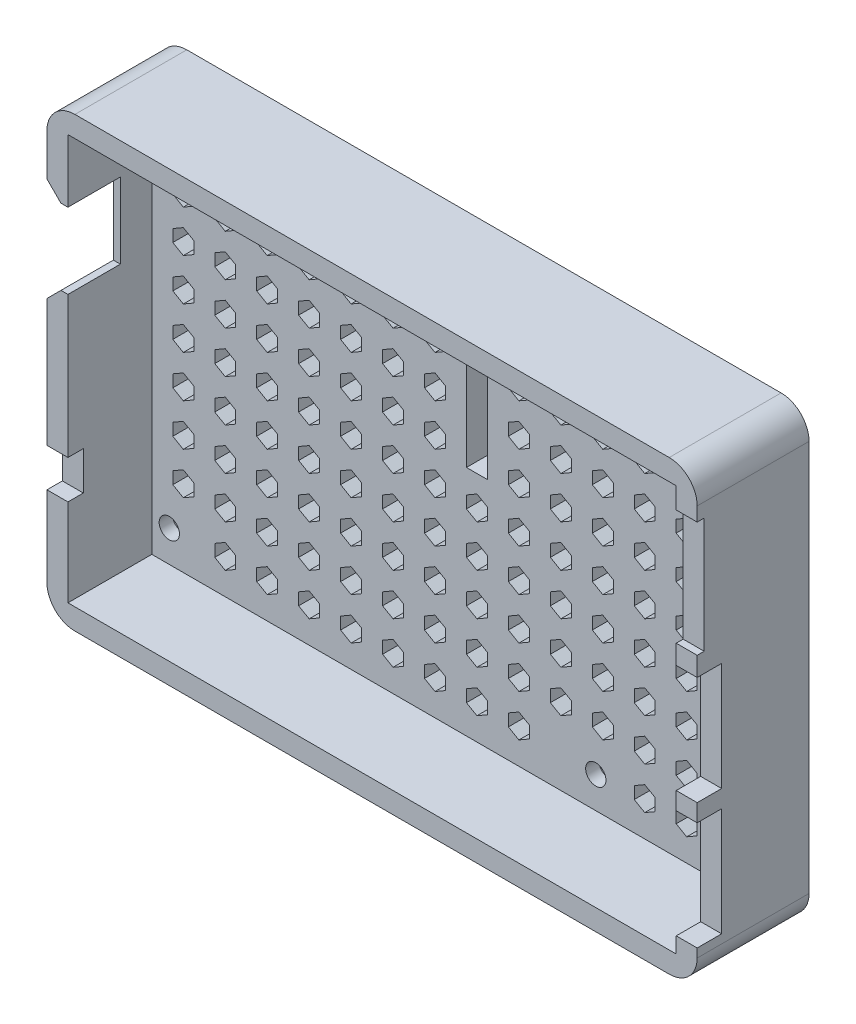
SolidWorks part; units mm, degrees
ref_plane "Přední rovina" through (0, 0, 0) normal (0, 0, 1) x (1, 0, 0)
ref_plane "Horní rovina" through (0, 0, 0) normal (0, 1, 0) x (1, 0, 0)
ref_plane "Pravá rovina" through (0, 0, 0) normal (1, 0, 0) x (0, 0, -1)
sketch "Base sketch" plane through (0, 0, 0) normal (0, 0, 1) x (1, 0, 0)
  line L1 (-46.5, 32) -> (46.5, 32)
  line L2 (-46.5, 32) -> (-46.5, -32)
  line L3 (-46.5, -32) -> (46.5, -32)
  line L4 (46.5, 32) -> (46.5, -32)
  line L5 (-46.5, 32) -> (46.5, -32) construction
  line L6 (-46.5, -32) -> (46.5, 32) construction
  point P0 (0, 0)
  dimension "D1" = 93
  dimension "D2" = 64
extrude "Base" add sketch "Base sketch" along normal blind 16
sketch "Inside cut sketch" plane through (0, 0, 16) normal (0, 0, 1) x (1, 0, 0)
  line L1 (-43.5, 29) -> (43.5, 29)
  line L2 (-43.5, 29) -> (-43.5, -29)
  line L3 (-43.5, -29) -> (43.5, -29)
  line L4 (43.5, 29) -> (43.5, -29)
  line L5 (-43.5, 29) -> (43.5, -29) construction
  line L6 (-43.5, -29) -> (43.5, 29) construction
  point P0 (0, 0)
  dimension "D1" = 58
  dimension "D2" = 87
extrude "Inside cut" cut sketch "Inside cut sketch" against normal blind 12
sketch "Front connectors sketch" plane through (46.5, 0, 0) normal (1, 0, 0) x (0, 0, -1)
  line L0 (-15, -32) -> (-15, 32)
  line L1 (-16, -32) -> (0, -32) construction
  line L2 (-16, 32) -> (0, 32) construction
  line L3 (-12.5, -32) -> (-12.5, 32)
  line L4 (-16, -32) -> (-16, 32) construction
  line L5 (-15, 26) -> (-16, 26)
  line L6 (-15, 26) -> (-15, 9.5)
  line L7 (-15, 9.5) -> (-16, 9.5)
  line L8 (-16, 26) -> (-16, 9.5)
  line L10 (-12.5, 6.75) -> (-16, 6.75)
  line L11 (-12.5, 6.75) -> (-12.5, -8.75)
  line L12 (-12.5, -8.75) -> (-16, -8.75)
  line L13 (-16, 6.75) -> (-16, -8.75)
  line L14 (-12.5, -11.25) -> (-16, -11.25)
  line L15 (-12.5, -11.25) -> (-12.5, -26.75)
  line L16 (-12.5, -26.75) -> (-16, -26.75)
  line L17 (-16, -11.25) -> (-16, -26.75)
  point P23 (-16, 17.75)
  point P25 (-16, -1)
  point P26 (-16, -19)
  dimension "D1" = 1
  dimension "D2" = 3.5
  dimension "D3" = 16.5
  dimension "D4" = 11.25
  dimension "D5" = 30
  dimension "D6" = 15.5
  dimension "D7" = 48
extrude "Front connectors" cut sketch "Front connectors sketch" against normal up to next contours L14 L17 L16 L15 | L12 L13 L10 L11 | L8 L7 L6 L5
sketch "Back connectors sketch" plane through (-46.5, 0, 0) normal (-1, 0, 0) x (0, 0, 1)
  line L0 (16, 32) -> (16, -32) construction
  line L1 (16, 20) -> (8.5, 20)
  line L2 (16, 20) -> (16, 9.2)
  line L3 (16, 9.2) -> (8.5, 9.2)
  line L4 (8.5, 20) -> (8.5, 9.2)
  line L6 (16, -11) -> (13.8, -11)
  line L7 (16, -11) -> (16, -16.5)
  line L8 (16, -16.5) -> (13.8, -16.5)
  line L9 (13.8, -11) -> (13.8, -16.5)
  dimension "D1" = 15.5
  dimension "D2" = 5.5
  dimension "D3" = 2.2
  dimension "D4" = 12
  dimension "D5" = 10.8
  dimension "D6" = 7.5
extrude "Back connectors" cut sketch "Back connectors sketch" against normal up to next
chamfer "Molex angle" distance 2 angle 45 3 edges at (-46.5, 9.2, 12.25) (-46.5, 20, 12.25) (-46.5, 14.6, 8.5)
sketch "Screw holes sketch" plane through (0, 0, 0) normal (0, 0, -1) x (-1, 0, 0)
  line L1 (-20, 24.5) -> (41, 24.5)
  line L2 (-20, 24.5) -> (-20, -24.5)
  line L3 (-20, -24.5) -> (41, -24.5)
  line L4 (41, 24.5) -> (41, -24.5)
  line L5 (-20, 24.5) -> (41, -24.5) construction
  line L6 (-20, -24.5) -> (41, 24.5) construction
  point P0 (10.5, 0)
  dimension "D1" = 5.5
  dimension "D2" = 7.5
  dimension "D3" = 49
  dimension "D4" = 61
hole_wizard "Screw holes" positions "Skica6" profile "Skica7" counterbore size "M2.5" standard "ISO" end condition through all
sketch "Skica6" plane through (0, 0, 0) normal (0, 0, -1) x (-1, 0, 0)
  point P0 (-20, -24.5)
  point P3 (-20, 24.5)
  point P6 (41, 24.5)
  point P9 (41, -24.5)
sketch "Skica7" plane through (20, -24.5, 0) normal (1, 0, 0) x (0, 1, 0)
  line L0 (0, 0) -> (0, 16)
  line L1 (0, 16) -> (1.45, 16)
  line L3 (1.45, 16) -> (1.45, 2.1)
  line L4 (1.45, 2.1) -> (3, 2.1)
  line L5 (3, 2.1) -> (3, 0)
  line L7 (3, 0) -> (0, 0)
  line L11 (0, -6.35) -> (0, 107.95) construction
  dimension "Průměr díry skrz" = 2.9
  dimension "Hloubka díry skrz" = 16
  dimension "Průměr válcového zahloubení" = 6
  dimension "Hloubka válcového zahloubení" = 2.1
fillet "Box rounding" radius 4 4 edges at (-46.5, -32, 8) (-46.5, 32, 8) (46.5, 32, 8) (46.5, -32, 8)
sketch "Ventilation holes sketch" plane through (0, 0, 0) normal (0, 0, -1) x (-1, 0, 0)
  line L0 (-42.5, 32) -> (42.5, 32) construction
  line L1 (-39, 22.2659) -> (-37.5, 23.1319)
  line L2 (-37.5, 23.1319) -> (-37.5, 24.864)
  line L3 (-37.5, 24.864) -> (-39, 25.73)
  line L4 (-39, 25.73) -> (-40.5, 24.864)
  line L5 (-40.5, 24.864) -> (-40.5, 23.1319)
  line L6 (-40.5, 23.1319) -> (-39, 22.2659)
  line L7 (-46.5, -28) -> (-46.5, 28) construction
  line L8 (-33, 22.2659) -> (-31.5, 23.1319)
  line L9 (-31.5, 23.1319) -> (-31.5, 24.864)
  line L10 (-31.5, 24.864) -> (-33, 25.73)
  line L11 (-33, 25.73) -> (-34.5, 24.864)
  line L12 (-34.5, 24.864) -> (-34.5, 23.1319)
  line L13 (-34.5, 23.1319) -> (-33, 22.2659)
  line L14 (-27, 22.2659) -> (-25.5, 23.1319)
  line L15 (-25.5, 23.1319) -> (-25.5, 24.864)
  line L16 (-25.5, 24.864) -> (-27, 25.73)
  line L17 (-27, 25.73) -> (-28.5, 24.864)
  line L18 (-28.5, 24.864) -> (-28.5, 23.1319)
  line L19 (-28.5, 23.1319) -> (-27, 22.2659)
  line L20 (-21, 22.2659) -> (-19.5, 23.1319)
  line L21 (-19.5, 23.1319) -> (-19.5, 24.864)
  line L22 (-19.5, 24.864) -> (-21, 25.73)
  line L23 (-21, 25.73) -> (-22.5, 24.864)
  line L24 (-22.5, 24.864) -> (-22.5, 23.1319)
  line L25 (-22.5, 23.1319) -> (-21, 22.2659)
  line L26 (-15, 22.2659) -> (-13.5, 23.1319)
  line L27 (-13.5, 23.1319) -> (-13.5, 24.864)
  line L28 (-13.5, 24.864) -> (-15, 25.73)
  line L29 (-15, 25.73) -> (-16.5, 24.864)
  line L30 (-16.5, 24.864) -> (-16.5, 23.1319)
  line L31 (-16.5, 23.1319) -> (-15, 22.2659)
  line L32 (-9, 22.2659) -> (-7.5, 23.1319)
  line L33 (-7.5, 23.1319) -> (-7.5, 24.864)
  line L34 (-7.5, 24.864) -> (-9, 25.73)
  line L35 (-9, 25.73) -> (-10.5, 24.864)
  line L36 (-10.5, 24.864) -> (-10.5, 23.1319)
  line L37 (-10.5, 23.1319) -> (-9, 22.2659)
  line L38 (-3, 22.2659) -> (-1.5, 23.1319)
  line L39 (-1.5, 23.1319) -> (-1.5, 24.864)
  line L40 (-1.5, 24.864) -> (-3, 25.73)
  line L41 (-3, 25.73) -> (-4.5, 24.864)
  line L42 (-4.5, 24.864) -> (-4.5, 23.1319)
  line L43 (-4.5, 23.1319) -> (-3, 22.2659)
  line L44 (3, 22.2659) -> (4.5, 23.1319)
  line L45 (4.5, 23.1319) -> (4.5, 24.864)
  line L46 (4.5, 24.864) -> (3, 25.73)
  line L47 (3, 25.73) -> (1.5, 24.864)
  line L48 (1.5, 24.864) -> (1.5, 23.1319)
  line L49 (1.5, 23.1319) -> (3, 22.2659)
  line L50 (9, 22.2659) -> (10.5, 23.1319)
  line L51 (10.5, 23.1319) -> (10.5, 24.864)
  line L52 (10.5, 24.864) -> (9, 25.73)
  line L53 (9, 25.73) -> (7.5, 24.864)
  line L54 (7.5, 24.864) -> (7.5, 23.1319)
  line L55 (7.5, 23.1319) -> (9, 22.2659)
  line L56 (15, 22.2659) -> (16.5, 23.1319)
  line L57 (16.5, 23.1319) -> (16.5, 24.864)
  line L58 (16.5, 24.864) -> (15, 25.73)
  line L59 (15, 25.73) -> (13.5, 24.864)
  line L60 (13.5, 24.864) -> (13.5, 23.1319)
  line L61 (13.5, 23.1319) -> (15, 22.2659)
  line L62 (21, 22.2659) -> (22.5, 23.1319)
  line L63 (22.5, 23.1319) -> (22.5, 24.864)
  line L64 (22.5, 24.864) -> (21, 25.73)
  line L65 (21, 25.73) -> (19.5, 24.864)
  line L66 (19.5, 24.864) -> (19.5, 23.1319)
  line L67 (19.5, 23.1319) -> (21, 22.2659)
  line L68 (27, 22.2659) -> (28.5, 23.1319)
  line L69 (28.5, 23.1319) -> (28.5, 24.864)
  line L70 (28.5, 24.864) -> (27, 25.73)
  line L71 (27, 25.73) -> (25.5, 24.864)
  line L72 (25.5, 24.864) -> (25.5, 23.1319)
  line L73 (25.5, 23.1319) -> (27, 22.2659)
  line L74 (33, 22.2659) -> (34.5, 23.1319)
  line L75 (34.5, 23.1319) -> (34.5, 24.864)
  line L76 (34.5, 24.864) -> (33, 25.73)
  line L77 (33, 25.73) -> (31.5, 24.864)
  line L78 (31.5, 24.864) -> (31.5, 23.1319)
  line L79 (31.5, 23.1319) -> (33, 22.2659)
  line L80 (39, 22.2659) -> (40.5, 23.1319)
  line L81 (40.5, 23.1319) -> (40.5, 24.864)
  line L82 (40.5, 24.864) -> (39, 25.73)
  line L83 (39, 25.73) -> (37.5, 24.864)
  line L84 (37.5, 24.864) -> (37.5, 23.1319)
  line L85 (37.5, 23.1319) -> (39, 22.2659)
  line L86 (-33, 16.2659) -> (-31.5, 17.1319)
  line L87 (-31.5, 17.1319) -> (-31.5, 18.864)
  line L88 (-31.5, 18.864) -> (-33, 19.73)
  line L89 (-33, 19.73) -> (-34.5, 18.864)
  line L90 (-34.5, 18.864) -> (-34.5, 17.1319)
  line L91 (-34.5, 17.1319) -> (-33, 16.2659)
  line L92 (-27, 16.2659) -> (-25.5, 17.1319)
  line L93 (-25.5, 17.1319) -> (-25.5, 18.864)
  line L94 (-25.5, 18.864) -> (-27, 19.73)
  line L95 (-27, 19.73) -> (-28.5, 18.864)
  line L96 (-28.5, 18.864) -> (-28.5, 17.1319)
  line L97 (-28.5, 17.1319) -> (-27, 16.2659)
  line L98 (-21, 16.2659) -> (-19.5, 17.1319)
  line L99 (-19.5, 17.1319) -> (-19.5, 18.864)
  line L100 (-19.5, 18.864) -> (-21, 19.73)
  line L101 (-21, 19.73) -> (-22.5, 18.864)
  line L102 (-22.5, 18.864) -> (-22.5, 17.1319)
  line L103 (-22.5, 17.1319) -> (-21, 16.2659)
  line L104 (-15, 16.2659) -> (-13.5, 17.1319)
  line L105 (-13.5, 17.1319) -> (-13.5, 18.864)
  line L106 (-13.5, 18.864) -> (-15, 19.73)
  line L107 (-15, 19.73) -> (-16.5, 18.864)
  line L108 (-16.5, 18.864) -> (-16.5, 17.1319)
  line L109 (-16.5, 17.1319) -> (-15, 16.2659)
  line L110 (-9, 16.2659) -> (-7.5, 17.1319)
  line L111 (-7.5, 17.1319) -> (-7.5, 18.864)
  line L112 (-7.5, 18.864) -> (-9, 19.73)
  line L113 (-9, 19.73) -> (-10.5, 18.864)
  line L114 (-10.5, 18.864) -> (-10.5, 17.1319)
  line L115 (-10.5, 17.1319) -> (-9, 16.2659)
  line L116 (-3, 16.2659) -> (-1.5, 17.1319)
  line L117 (-1.5, 17.1319) -> (-1.5, 18.864)
  line L118 (-1.5, 18.864) -> (-3, 19.73)
  line L119 (-3, 19.73) -> (-4.5, 18.864)
  line L120 (-4.5, 18.864) -> (-4.5, 17.1319)
  line L121 (-4.5, 17.1319) -> (-3, 16.2659)
  line L122 (3, 16.2659) -> (4.5, 17.1319)
  line L123 (4.5, 17.1319) -> (4.5, 18.864)
  line L124 (4.5, 18.864) -> (3, 19.73)
  line L125 (3, 19.73) -> (1.5, 18.864)
  line L126 (1.5, 18.864) -> (1.5, 17.1319)
  line L127 (1.5, 17.1319) -> (3, 16.2659)
  line L128 (9, 16.2659) -> (10.5, 17.1319)
  line L129 (10.5, 17.1319) -> (10.5, 18.864)
  line L130 (10.5, 18.864) -> (9, 19.73)
  line L131 (9, 19.73) -> (7.5, 18.864)
  line L132 (7.5, 18.864) -> (7.5, 17.1319)
  line L133 (7.5, 17.1319) -> (9, 16.2659)
  line L134 (15, 16.2659) -> (16.5, 17.1319)
  line L135 (16.5, 17.1319) -> (16.5, 18.864)
  line L136 (16.5, 18.864) -> (15, 19.73)
  line L137 (15, 19.73) -> (13.5, 18.864)
  line L138 (13.5, 18.864) -> (13.5, 17.1319)
  line L139 (13.5, 17.1319) -> (15, 16.2659)
  line L140 (21, 16.2659) -> (22.5, 17.1319)
  line L141 (22.5, 17.1319) -> (22.5, 18.864)
  line L142 (22.5, 18.864) -> (21, 19.73)
  line L143 (21, 19.73) -> (19.5, 18.864)
  line L144 (19.5, 18.864) -> (19.5, 17.1319)
  line L145 (19.5, 17.1319) -> (21, 16.2659)
  line L146 (27, 16.2659) -> (28.5, 17.1319)
  line L147 (28.5, 17.1319) -> (28.5, 18.864)
  line L148 (28.5, 18.864) -> (27, 19.73)
  line L149 (27, 19.73) -> (25.5, 18.864)
  line L150 (25.5, 18.864) -> (25.5, 17.1319)
  line L151 (25.5, 17.1319) -> (27, 16.2659)
  line L152 (33, 16.2659) -> (34.5, 17.1319)
  line L153 (34.5, 17.1319) -> (34.5, 18.864)
  line L154 (34.5, 18.864) -> (33, 19.73)
  line L155 (33, 19.73) -> (31.5, 18.864)
  line L156 (31.5, 18.864) -> (31.5, 17.1319)
  line L157 (31.5, 17.1319) -> (33, 16.2659)
  line L158 (39, 16.2659) -> (40.5, 17.1319)
  line L159 (40.5, 17.1319) -> (40.5, 18.864)
  line L160 (40.5, 18.864) -> (39, 19.73)
  line L161 (39, 19.73) -> (37.5, 18.864)
  line L162 (37.5, 18.864) -> (37.5, 17.1319)
  line L163 (37.5, 17.1319) -> (39, 16.2659)
  line L164 (-33, 10.2659) -> (-31.5, 11.1319)
  line L165 (-31.5, 11.1319) -> (-31.5, 12.864)
  line L166 (-31.5, 12.864) -> (-33, 13.73)
  line L167 (-33, 13.73) -> (-34.5, 12.864)
  line L168 (-34.5, 12.864) -> (-34.5, 11.1319)
  line L169 (-34.5, 11.1319) -> (-33, 10.2659)
  line L170 (-27, 10.2659) -> (-25.5, 11.1319)
  line L171 (-25.5, 11.1319) -> (-25.5, 12.864)
  line L172 (-25.5, 12.864) -> (-27, 13.73)
  line L173 (-27, 13.73) -> (-28.5, 12.864)
  line L174 (-28.5, 12.864) -> (-28.5, 11.1319)
  line L175 (-28.5, 11.1319) -> (-27, 10.2659)
  line L176 (-21, 10.2659) -> (-19.5, 11.1319)
  line L177 (-19.5, 11.1319) -> (-19.5, 12.864)
  line L178 (-19.5, 12.864) -> (-21, 13.73)
  line L179 (-21, 13.73) -> (-22.5, 12.864)
  line L180 (-22.5, 12.864) -> (-22.5, 11.1319)
  line L181 (-22.5, 11.1319) -> (-21, 10.2659)
  line L182 (-15, 10.2659) -> (-13.5, 11.1319)
  line L183 (-13.5, 11.1319) -> (-13.5, 12.864)
  line L184 (-13.5, 12.864) -> (-15, 13.73)
  line L185 (-15, 13.73) -> (-16.5, 12.864)
  line L186 (-16.5, 12.864) -> (-16.5, 11.1319)
  line L187 (-16.5, 11.1319) -> (-15, 10.2659)
  line L188 (-9, 10.2659) -> (-7.5, 11.1319)
  line L189 (-7.5, 11.1319) -> (-7.5, 12.864)
  line L190 (-7.5, 12.864) -> (-9, 13.73)
  line L191 (-9, 13.73) -> (-10.5, 12.864)
  line L192 (-10.5, 12.864) -> (-10.5, 11.1319)
  line L193 (-10.5, 11.1319) -> (-9, 10.2659)
  line L194 (-3, 10.2659) -> (-1.5, 11.1319)
  line L195 (-1.5, 11.1319) -> (-1.5, 12.864)
  line L196 (-1.5, 12.864) -> (-3, 13.73)
  line L197 (-3, 13.73) -> (-4.5, 12.864)
  line L198 (-4.5, 12.864) -> (-4.5, 11.1319)
  line L199 (-4.5, 11.1319) -> (-3, 10.2659)
  line L200 (3, 10.2659) -> (4.5, 11.1319)
  line L201 (4.5, 11.1319) -> (4.5, 12.864)
  line L202 (4.5, 12.864) -> (3, 13.73)
  line L203 (3, 13.73) -> (1.5, 12.864)
  line L204 (1.5, 12.864) -> (1.5, 11.1319)
  line L205 (1.5, 11.1319) -> (3, 10.2659)
  line L206 (9, 10.2659) -> (10.5, 11.1319)
  line L207 (10.5, 11.1319) -> (10.5, 12.864)
  line L208 (10.5, 12.864) -> (9, 13.73)
  line L209 (9, 13.73) -> (7.5, 12.864)
  line L210 (7.5, 12.864) -> (7.5, 11.1319)
  line L211 (7.5, 11.1319) -> (9, 10.2659)
  line L212 (15, 10.2659) -> (16.5, 11.1319)
  line L213 (16.5, 11.1319) -> (16.5, 12.864)
  line L214 (16.5, 12.864) -> (15, 13.73)
  line L215 (15, 13.73) -> (13.5, 12.864)
  line L216 (13.5, 12.864) -> (13.5, 11.1319)
  line L217 (13.5, 11.1319) -> (15, 10.2659)
  line L218 (21, 10.2659) -> (22.5, 11.1319)
  line L219 (22.5, 11.1319) -> (22.5, 12.864)
  line L220 (22.5, 12.864) -> (21, 13.73)
  line L221 (21, 13.73) -> (19.5, 12.864)
  line L222 (19.5, 12.864) -> (19.5, 11.1319)
  line L223 (19.5, 11.1319) -> (21, 10.2659)
  line L224 (27, 10.2659) -> (28.5, 11.1319)
  line L225 (28.5, 11.1319) -> (28.5, 12.864)
  line L226 (28.5, 12.864) -> (27, 13.73)
  line L227 (27, 13.73) -> (25.5, 12.864)
  line L228 (25.5, 12.864) -> (25.5, 11.1319)
  line L229 (25.5, 11.1319) -> (27, 10.2659)
  line L230 (33, 10.2659) -> (34.5, 11.1319)
  line L231 (34.5, 11.1319) -> (34.5, 12.864)
  line L232 (34.5, 12.864) -> (33, 13.73)
  line L233 (33, 13.73) -> (31.5, 12.864)
  line L234 (31.5, 12.864) -> (31.5, 11.1319)
  line L235 (31.5, 11.1319) -> (33, 10.2659)
  line L236 (39, 10.2659) -> (40.5, 11.1319)
  line L237 (40.5, 11.1319) -> (40.5, 12.864)
  line L238 (40.5, 12.864) -> (39, 13.73)
  line L239 (39, 13.73) -> (37.5, 12.864)
  line L240 (37.5, 12.864) -> (37.5, 11.1319)
  line L241 (37.5, 11.1319) -> (39, 10.2659)
  line L242 (-33, 4.2659) -> (-31.5, 5.1319)
  line L243 (-31.5, 5.1319) -> (-31.5, 6.864)
  line L244 (-31.5, 6.864) -> (-33, 7.73)
  line L245 (-33, 7.73) -> (-34.5, 6.864)
  line L246 (-34.5, 6.864) -> (-34.5, 5.1319)
  line L247 (-34.5, 5.1319) -> (-33, 4.2659)
  line L248 (-27, 4.2659) -> (-25.5, 5.1319)
  line L249 (-25.5, 5.1319) -> (-25.5, 6.864)
  line L250 (-25.5, 6.864) -> (-27, 7.73)
  line L251 (-27, 7.73) -> (-28.5, 6.864)
  line L252 (-28.5, 6.864) -> (-28.5, 5.1319)
  line L253 (-28.5, 5.1319) -> (-27, 4.2659)
  line L254 (-21, 4.2659) -> (-19.5, 5.1319)
  line L255 (-19.5, 5.1319) -> (-19.5, 6.864)
  line L256 (-19.5, 6.864) -> (-21, 7.73)
  line L257 (-21, 7.73) -> (-22.5, 6.864)
  line L258 (-22.5, 6.864) -> (-22.5, 5.1319)
  line L259 (-22.5, 5.1319) -> (-21, 4.2659)
  line L260 (-15, 4.2659) -> (-13.5, 5.1319)
  line L261 (-13.5, 5.1319) -> (-13.5, 6.864)
  line L262 (-13.5, 6.864) -> (-15, 7.73)
  line L263 (-15, 7.73) -> (-16.5, 6.864)
  line L264 (-16.5, 6.864) -> (-16.5, 5.1319)
  line L265 (-16.5, 5.1319) -> (-15, 4.2659)
  line L266 (-9, 4.2659) -> (-7.5, 5.1319)
  line L267 (-7.5, 5.1319) -> (-7.5, 6.864)
  line L268 (-7.5, 6.864) -> (-9, 7.73)
  line L269 (-9, 7.73) -> (-10.5, 6.864)
  line L270 (-10.5, 6.864) -> (-10.5, 5.1319)
  line L271 (-10.5, 5.1319) -> (-9, 4.2659)
  line L272 (-3, 4.2659) -> (-1.5, 5.1319)
  line L273 (-1.5, 5.1319) -> (-1.5, 6.864)
  line L274 (-1.5, 6.864) -> (-3, 7.73)
  line L275 (-3, 7.73) -> (-4.5, 6.864)
  line L276 (-4.5, 6.864) -> (-4.5, 5.1319)
  line L277 (-4.5, 5.1319) -> (-3, 4.2659)
  line L278 (3, 4.2659) -> (4.5, 5.1319)
  line L279 (4.5, 5.1319) -> (4.5, 6.864)
  line L280 (4.5, 6.864) -> (3, 7.73)
  line L281 (3, 7.73) -> (1.5, 6.864)
  line L282 (1.5, 6.864) -> (1.5, 5.1319)
  line L283 (1.5, 5.1319) -> (3, 4.2659)
  line L284 (9, 4.2659) -> (10.5, 5.1319)
  line L285 (10.5, 5.1319) -> (10.5, 6.864)
  line L286 (10.5, 6.864) -> (9, 7.73)
  line L287 (9, 7.73) -> (7.5, 6.864)
  line L288 (7.5, 6.864) -> (7.5, 5.1319)
  line L289 (7.5, 5.1319) -> (9, 4.2659)
  line L290 (15, 4.2659) -> (16.5, 5.1319)
  line L291 (16.5, 5.1319) -> (16.5, 6.864)
  line L292 (16.5, 6.864) -> (15, 7.73)
  line L293 (15, 7.73) -> (13.5, 6.864)
  line L294 (13.5, 6.864) -> (13.5, 5.1319)
  line L295 (13.5, 5.1319) -> (15, 4.2659)
  line L296 (21, 4.2659) -> (22.5, 5.1319)
  line L297 (22.5, 5.1319) -> (22.5, 6.864)
  line L298 (22.5, 6.864) -> (21, 7.73)
  line L299 (21, 7.73) -> (19.5, 6.864)
  line L300 (19.5, 6.864) -> (19.5, 5.1319)
  line L301 (19.5, 5.1319) -> (21, 4.2659)
  line L302 (27, 4.2659) -> (28.5, 5.1319)
  line L303 (28.5, 5.1319) -> (28.5, 6.864)
  line L304 (28.5, 6.864) -> (27, 7.73)
  line L305 (27, 7.73) -> (25.5, 6.864)
  line L306 (25.5, 6.864) -> (25.5, 5.1319)
  line L307 (25.5, 5.1319) -> (27, 4.2659)
  line L308 (33, 4.2659) -> (34.5, 5.1319)
  line L309 (34.5, 5.1319) -> (34.5, 6.864)
  line L310 (34.5, 6.864) -> (33, 7.73)
  line L311 (33, 7.73) -> (31.5, 6.864)
  line L312 (31.5, 6.864) -> (31.5, 5.1319)
  line L313 (31.5, 5.1319) -> (33, 4.2659)
  line L314 (39, 4.2659) -> (40.5, 5.1319)
  line L315 (40.5, 5.1319) -> (40.5, 6.864)
  line L316 (40.5, 6.864) -> (39, 7.73)
  line L317 (39, 7.73) -> (37.5, 6.864)
  line L318 (37.5, 6.864) -> (37.5, 5.1319)
  line L319 (37.5, 5.1319) -> (39, 4.2659)
  line L320 (-33, -1.7341) -> (-31.5, -0.8681)
  line L321 (-31.5, -0.8681) -> (-31.5, 0.864)
  line L322 (-31.5, 0.864) -> (-33, 1.73)
  line L323 (-33, 1.73) -> (-34.5, 0.864)
  line L324 (-34.5, 0.864) -> (-34.5, -0.8681)
  line L325 (-34.5, -0.8681) -> (-33, -1.7341)
  line L326 (-27, -1.7341) -> (-25.5, -0.8681)
  line L327 (-25.5, -0.8681) -> (-25.5, 0.864)
  line L328 (-25.5, 0.864) -> (-27, 1.73)
  line L329 (-27, 1.73) -> (-28.5, 0.864)
  line L330 (-28.5, 0.864) -> (-28.5, -0.8681)
  line L331 (-28.5, -0.8681) -> (-27, -1.7341)
  line L332 (-21, -1.7341) -> (-19.5, -0.8681)
  line L333 (-19.5, -0.8681) -> (-19.5, 0.864)
  line L334 (-19.5, 0.864) -> (-21, 1.73)
  line L335 (-21, 1.73) -> (-22.5, 0.864)
  line L336 (-22.5, 0.864) -> (-22.5, -0.8681)
  line L337 (-22.5, -0.8681) -> (-21, -1.7341)
  line L338 (-15, -1.7341) -> (-13.5, -0.8681)
  line L339 (-13.5, -0.8681) -> (-13.5, 0.864)
  line L340 (-13.5, 0.864) -> (-15, 1.73)
  line L341 (-15, 1.73) -> (-16.5, 0.864)
  line L342 (-16.5, 0.864) -> (-16.5, -0.8681)
  line L343 (-16.5, -0.8681) -> (-15, -1.7341)
  line L344 (-9, -1.7341) -> (-7.5, -0.8681)
  line L345 (-7.5, -0.8681) -> (-7.5, 0.864)
  line L346 (-7.5, 0.864) -> (-9, 1.73)
  line L347 (-9, 1.73) -> (-10.5, 0.864)
  line L348 (-10.5, 0.864) -> (-10.5, -0.8681)
  line L349 (-10.5, -0.8681) -> (-9, -1.7341)
  line L350 (-3, -1.7341) -> (-1.5, -0.8681)
  line L351 (-1.5, -0.8681) -> (-1.5, 0.864)
  line L352 (-1.5, 0.864) -> (-3, 1.73)
  line L353 (-3, 1.73) -> (-4.5, 0.864)
  line L354 (-4.5, 0.864) -> (-4.5, -0.8681)
  line L355 (-4.5, -0.8681) -> (-3, -1.7341)
  line L356 (3, -1.7341) -> (4.5, -0.8681)
  line L357 (4.5, -0.8681) -> (4.5, 0.864)
  line L358 (4.5, 0.864) -> (3, 1.73)
  line L359 (3, 1.73) -> (1.5, 0.864)
  line L360 (1.5, 0.864) -> (1.5, -0.8681)
  line L361 (1.5, -0.8681) -> (3, -1.7341)
  line L362 (9, -1.7341) -> (10.5, -0.8681)
  line L363 (10.5, -0.8681) -> (10.5, 0.864)
  line L364 (10.5, 0.864) -> (9, 1.73)
  line L365 (9, 1.73) -> (7.5, 0.864)
  line L366 (7.5, 0.864) -> (7.5, -0.8681)
  line L367 (7.5, -0.8681) -> (9, -1.7341)
  line L368 (15, -1.7341) -> (16.5, -0.8681)
  line L369 (16.5, -0.8681) -> (16.5, 0.864)
  line L370 (16.5, 0.864) -> (15, 1.73)
  line L371 (15, 1.73) -> (13.5, 0.864)
  line L372 (13.5, 0.864) -> (13.5, -0.8681)
  line L373 (13.5, -0.8681) -> (15, -1.7341)
  line L374 (21, -1.7341) -> (22.5, -0.8681)
  line L375 (22.5, -0.8681) -> (22.5, 0.864)
  line L376 (22.5, 0.864) -> (21, 1.73)
  line L377 (21, 1.73) -> (19.5, 0.864)
  line L378 (19.5, 0.864) -> (19.5, -0.8681)
  line L379 (19.5, -0.8681) -> (21, -1.7341)
  line L380 (27, -1.7341) -> (28.5, -0.8681)
  line L381 (28.5, -0.8681) -> (28.5, 0.864)
  line L382 (28.5, 0.864) -> (27, 1.73)
  line L383 (27, 1.73) -> (25.5, 0.864)
  line L384 (25.5, 0.864) -> (25.5, -0.8681)
  line L385 (25.5, -0.8681) -> (27, -1.7341)
  line L386 (33, -1.7341) -> (34.5, -0.8681)
  line L387 (34.5, -0.8681) -> (34.5, 0.864)
  line L388 (34.5, 0.864) -> (33, 1.73)
  line L389 (33, 1.73) -> (31.5, 0.864)
  line L390 (31.5, 0.864) -> (31.5, -0.8681)
  line L391 (31.5, -0.8681) -> (33, -1.7341)
  line L392 (39, -1.7341) -> (40.5, -0.8681)
  line L393 (40.5, -0.8681) -> (40.5, 0.864)
  line L394 (40.5, 0.864) -> (39, 1.73)
  line L395 (39, 1.73) -> (37.5, 0.864)
  line L396 (37.5, 0.864) -> (37.5, -0.8681)
  line L397 (37.5, -0.8681) -> (39, -1.7341)
  line L398 (-33, -7.7341) -> (-31.5, -6.8681)
  line L399 (-31.5, -6.8681) -> (-31.5, -5.136)
  line L400 (-31.5, -5.136) -> (-33, -4.27)
  line L401 (-33, -4.27) -> (-34.5, -5.136)
  line L402 (-34.5, -5.136) -> (-34.5, -6.8681)
  line L403 (-34.5, -6.8681) -> (-33, -7.7341)
  line L404 (-27, -7.7341) -> (-25.5, -6.8681)
  line L405 (-25.5, -6.8681) -> (-25.5, -5.136)
  line L406 (-25.5, -5.136) -> (-27, -4.27)
  line L407 (-27, -4.27) -> (-28.5, -5.136)
  line L408 (-28.5, -5.136) -> (-28.5, -6.8681)
  line L409 (-28.5, -6.8681) -> (-27, -7.7341)
  line L410 (-21, -7.7341) -> (-19.5, -6.8681)
  line L411 (-19.5, -6.8681) -> (-19.5, -5.136)
  line L412 (-19.5, -5.136) -> (-21, -4.27)
  line L413 (-21, -4.27) -> (-22.5, -5.136)
  line L414 (-22.5, -5.136) -> (-22.5, -6.8681)
  line L415 (-22.5, -6.8681) -> (-21, -7.7341)
  line L416 (-15, -7.7341) -> (-13.5, -6.8681)
  line L417 (-13.5, -6.8681) -> (-13.5, -5.136)
  line L418 (-13.5, -5.136) -> (-15, -4.27)
  line L419 (-15, -4.27) -> (-16.5, -5.136)
  line L420 (-16.5, -5.136) -> (-16.5, -6.8681)
  line L421 (-16.5, -6.8681) -> (-15, -7.7341)
  line L422 (-9, -7.7341) -> (-7.5, -6.8681)
  line L423 (-7.5, -6.8681) -> (-7.5, -5.136)
  line L424 (-7.5, -5.136) -> (-9, -4.27)
  line L425 (-9, -4.27) -> (-10.5, -5.136)
  line L426 (-10.5, -5.136) -> (-10.5, -6.8681)
  line L427 (-10.5, -6.8681) -> (-9, -7.7341)
  line L428 (-3, -7.7341) -> (-1.5, -6.8681)
  line L429 (-1.5, -6.8681) -> (-1.5, -5.136)
  line L430 (-1.5, -5.136) -> (-3, -4.27)
  line L431 (-3, -4.27) -> (-4.5, -5.136)
  line L432 (-4.5, -5.136) -> (-4.5, -6.8681)
  line L433 (-4.5, -6.8681) -> (-3, -7.7341)
  line L434 (3, -7.7341) -> (4.5, -6.8681)
  line L435 (4.5, -6.8681) -> (4.5, -5.136)
  line L436 (4.5, -5.136) -> (3, -4.27)
  line L437 (3, -4.27) -> (1.5, -5.136)
  line L438 (1.5, -5.136) -> (1.5, -6.8681)
  line L439 (1.5, -6.8681) -> (3, -7.7341)
  line L440 (9, -7.7341) -> (10.5, -6.8681)
  line L441 (10.5, -6.8681) -> (10.5, -5.136)
  line L442 (10.5, -5.136) -> (9, -4.27)
  line L443 (9, -4.27) -> (7.5, -5.136)
  line L444 (7.5, -5.136) -> (7.5, -6.8681)
  line L445 (7.5, -6.8681) -> (9, -7.7341)
  line L446 (15, -7.7341) -> (16.5, -6.8681)
  line L447 (16.5, -6.8681) -> (16.5, -5.136)
  line L448 (16.5, -5.136) -> (15, -4.27)
  line L449 (15, -4.27) -> (13.5, -5.136)
  line L450 (13.5, -5.136) -> (13.5, -6.8681)
  line L451 (13.5, -6.8681) -> (15, -7.7341)
  line L452 (21, -7.7341) -> (22.5, -6.8681)
  line L453 (22.5, -6.8681) -> (22.5, -5.136)
  line L454 (22.5, -5.136) -> (21, -4.27)
  line L455 (21, -4.27) -> (19.5, -5.136)
  line L456 (19.5, -5.136) -> (19.5, -6.8681)
  line L457 (19.5, -6.8681) -> (21, -7.7341)
  line L458 (27, -7.7341) -> (28.5, -6.8681)
  line L459 (28.5, -6.8681) -> (28.5, -5.136)
  line L460 (28.5, -5.136) -> (27, -4.27)
  line L461 (27, -4.27) -> (25.5, -5.136)
  line L462 (25.5, -5.136) -> (25.5, -6.8681)
  line L463 (25.5, -6.8681) -> (27, -7.7341)
  line L464 (33, -7.7341) -> (34.5, -6.8681)
  line L465 (34.5, -6.8681) -> (34.5, -5.136)
  line L466 (34.5, -5.136) -> (33, -4.27)
  line L467 (33, -4.27) -> (31.5, -5.136)
  line L468 (31.5, -5.136) -> (31.5, -6.8681)
  line L469 (31.5, -6.8681) -> (33, -7.7341)
  line L470 (39, -7.7341) -> (40.5, -6.8681)
  line L471 (40.5, -6.8681) -> (40.5, -5.136)
  line L472 (40.5, -5.136) -> (39, -4.27)
  line L473 (39, -4.27) -> (37.5, -5.136)
  line L474 (37.5, -5.136) -> (37.5, -6.8681)
  line L475 (37.5, -6.8681) -> (39, -7.7341)
  line L476 (-33, -13.7341) -> (-31.5, -12.8681)
  line L477 (-31.5, -12.8681) -> (-31.5, -11.136)
  line L478 (-31.5, -11.136) -> (-33, -10.27)
  line L479 (-33, -10.27) -> (-34.5, -11.136)
  line L480 (-34.5, -11.136) -> (-34.5, -12.8681)
  line L481 (-34.5, -12.8681) -> (-33, -13.7341)
  line L482 (-27, -13.7341) -> (-25.5, -12.8681)
  line L483 (-25.5, -12.8681) -> (-25.5, -11.136)
  line L484 (-25.5, -11.136) -> (-27, -10.27)
  line L485 (-27, -10.27) -> (-28.5, -11.136)
  line L486 (-28.5, -11.136) -> (-28.5, -12.8681)
  line L487 (-28.5, -12.8681) -> (-27, -13.7341)
  line L488 (-21, -13.7341) -> (-19.5, -12.8681)
  line L489 (-19.5, -12.8681) -> (-19.5, -11.136)
  line L490 (-19.5, -11.136) -> (-21, -10.27)
  line L491 (-21, -10.27) -> (-22.5, -11.136)
  line L492 (-22.5, -11.136) -> (-22.5, -12.8681)
  line L493 (-22.5, -12.8681) -> (-21, -13.7341)
  line L494 (-15, -13.7341) -> (-13.5, -12.8681)
  line L495 (-13.5, -12.8681) -> (-13.5, -11.136)
  line L496 (-13.5, -11.136) -> (-15, -10.27)
  line L497 (-15, -10.27) -> (-16.5, -11.136)
  line L498 (-16.5, -11.136) -> (-16.5, -12.8681)
  line L499 (-16.5, -12.8681) -> (-15, -13.7341)
  line L500 (-9, -13.7341) -> (-7.5, -12.8681)
  line L501 (-7.5, -12.8681) -> (-7.5, -11.136)
  line L502 (-7.5, -11.136) -> (-9, -10.27)
  line L503 (-9, -10.27) -> (-10.5, -11.136)
  line L504 (-10.5, -11.136) -> (-10.5, -12.8681)
  line L505 (-10.5, -12.8681) -> (-9, -13.7341)
  line L506 (-3, -13.7341) -> (-1.5, -12.8681)
  line L507 (-1.5, -12.8681) -> (-1.5, -11.136)
  line L508 (-1.5, -11.136) -> (-3, -10.27)
  line L509 (-3, -10.27) -> (-4.5, -11.136)
  line L510 (-4.5, -11.136) -> (-4.5, -12.8681)
  line L511 (-4.5, -12.8681) -> (-3, -13.7341)
  line L512 (3, -13.7341) -> (4.5, -12.8681)
  line L513 (4.5, -12.8681) -> (4.5, -11.136)
  line L514 (4.5, -11.136) -> (3, -10.27)
  line L515 (3, -10.27) -> (1.5, -11.136)
  line L516 (1.5, -11.136) -> (1.5, -12.8681)
  line L517 (1.5, -12.8681) -> (3, -13.7341)
  line L518 (9, -13.7341) -> (10.5, -12.8681)
  line L519 (10.5, -12.8681) -> (10.5, -11.136)
  line L520 (10.5, -11.136) -> (9, -10.27)
  line L521 (9, -10.27) -> (7.5, -11.136)
  line L522 (7.5, -11.136) -> (7.5, -12.8681)
  line L523 (7.5, -12.8681) -> (9, -13.7341)
  line L524 (15, -13.7341) -> (16.5, -12.8681)
  line L525 (16.5, -12.8681) -> (16.5, -11.136)
  line L526 (16.5, -11.136) -> (15, -10.27)
  line L527 (15, -10.27) -> (13.5, -11.136)
  line L528 (13.5, -11.136) -> (13.5, -12.8681)
  line L529 (13.5, -12.8681) -> (15, -13.7341)
  line L530 (21, -13.7341) -> (22.5, -12.8681)
  line L531 (22.5, -12.8681) -> (22.5, -11.136)
  line L532 (22.5, -11.136) -> (21, -10.27)
  line L533 (21, -10.27) -> (19.5, -11.136)
  line L534 (19.5, -11.136) -> (19.5, -12.8681)
  line L535 (19.5, -12.8681) -> (21, -13.7341)
  line L536 (27, -13.7341) -> (28.5, -12.8681)
  line L537 (28.5, -12.8681) -> (28.5, -11.136)
  line L538 (28.5, -11.136) -> (27, -10.27)
  line L539 (27, -10.27) -> (25.5, -11.136)
  line L540 (25.5, -11.136) -> (25.5, -12.8681)
  line L541 (25.5, -12.8681) -> (27, -13.7341)
  line L542 (33, -13.7341) -> (34.5, -12.8681)
  line L543 (34.5, -12.8681) -> (34.5, -11.136)
  line L544 (34.5, -11.136) -> (33, -10.27)
  line L545 (33, -10.27) -> (31.5, -11.136)
  line L546 (31.5, -11.136) -> (31.5, -12.8681)
  line L547 (31.5, -12.8681) -> (33, -13.7341)
  line L548 (39, -13.7341) -> (40.5, -12.8681)
  line L549 (40.5, -12.8681) -> (40.5, -11.136)
  line L550 (40.5, -11.136) -> (39, -10.27)
  line L551 (39, -10.27) -> (37.5, -11.136)
  line L552 (37.5, -11.136) -> (37.5, -12.8681)
  line L553 (37.5, -12.8681) -> (39, -13.7341)
  line L554 (-33, -19.7341) -> (-31.5, -18.8681)
  line L555 (-31.5, -18.8681) -> (-31.5, -17.136)
  line L556 (-31.5, -17.136) -> (-33, -16.27)
  line L557 (-33, -16.27) -> (-34.5, -17.136)
  line L558 (-34.5, -17.136) -> (-34.5, -18.8681)
  line L559 (-34.5, -18.8681) -> (-33, -19.7341)
  line L560 (-27, -19.7341) -> (-25.5, -18.8681)
  line L561 (-25.5, -18.8681) -> (-25.5, -17.136)
  line L562 (-25.5, -17.136) -> (-27, -16.27)
  line L563 (-27, -16.27) -> (-28.5, -17.136)
  line L564 (-28.5, -17.136) -> (-28.5, -18.8681)
  line L565 (-28.5, -18.8681) -> (-27, -19.7341)
  line L566 (-21, -19.7341) -> (-19.5, -18.8681)
  line L567 (-19.5, -18.8681) -> (-19.5, -17.136)
  line L568 (-19.5, -17.136) -> (-21, -16.27)
  line L569 (-21, -16.27) -> (-22.5, -17.136)
  line L570 (-22.5, -17.136) -> (-22.5, -18.8681)
  line L571 (-22.5, -18.8681) -> (-21, -19.7341)
  line L572 (-15, -19.7341) -> (-13.5, -18.8681)
  line L573 (-13.5, -18.8681) -> (-13.5, -17.136)
  line L574 (-13.5, -17.136) -> (-15, -16.27)
  line L575 (-15, -16.27) -> (-16.5, -17.136)
  line L576 (-16.5, -17.136) -> (-16.5, -18.8681)
  line L577 (-16.5, -18.8681) -> (-15, -19.7341)
  line L578 (-9, -19.7341) -> (-7.5, -18.8681)
  line L579 (-7.5, -18.8681) -> (-7.5, -17.136)
  line L580 (-7.5, -17.136) -> (-9, -16.27)
  line L581 (-9, -16.27) -> (-10.5, -17.136)
  line L582 (-10.5, -17.136) -> (-10.5, -18.8681)
  line L583 (-10.5, -18.8681) -> (-9, -19.7341)
  line L584 (-3, -19.7341) -> (-1.5, -18.8681)
  line L585 (-1.5, -18.8681) -> (-1.5, -17.136)
  line L586 (-1.5, -17.136) -> (-3, -16.27)
  line L587 (-3, -16.27) -> (-4.5, -17.136)
  line L588 (-4.5, -17.136) -> (-4.5, -18.8681)
  line L589 (-4.5, -18.8681) -> (-3, -19.7341)
  line L590 (3, -19.7341) -> (4.5, -18.8681)
  line L591 (4.5, -18.8681) -> (4.5, -17.136)
  line L592 (4.5, -17.136) -> (3, -16.27)
  line L593 (3, -16.27) -> (1.5, -17.136)
  line L594 (1.5, -17.136) -> (1.5, -18.8681)
  line L595 (1.5, -18.8681) -> (3, -19.7341)
  line L596 (9, -19.7341) -> (10.5, -18.8681)
  line L597 (10.5, -18.8681) -> (10.5, -17.136)
  line L598 (10.5, -17.136) -> (9, -16.27)
  line L599 (9, -16.27) -> (7.5, -17.136)
  line L600 (7.5, -17.136) -> (7.5, -18.8681)
  line L601 (7.5, -18.8681) -> (9, -19.7341)
  line L602 (15, -19.7341) -> (16.5, -18.8681)
  line L603 (16.5, -18.8681) -> (16.5, -17.136)
  line L604 (16.5, -17.136) -> (15, -16.27)
  line L605 (15, -16.27) -> (13.5, -17.136)
  line L606 (13.5, -17.136) -> (13.5, -18.8681)
  line L607 (13.5, -18.8681) -> (15, -19.7341)
  line L608 (21, -19.7341) -> (22.5, -18.8681)
  line L609 (22.5, -18.8681) -> (22.5, -17.136)
  line L610 (22.5, -17.136) -> (21, -16.27)
  line L611 (21, -16.27) -> (19.5, -17.136)
  line L612 (19.5, -17.136) -> (19.5, -18.8681)
  line L613 (19.5, -18.8681) -> (21, -19.7341)
  line L614 (27, -19.7341) -> (28.5, -18.8681)
  line L615 (28.5, -18.8681) -> (28.5, -17.136)
  line L616 (28.5, -17.136) -> (27, -16.27)
  line L617 (27, -16.27) -> (25.5, -17.136)
  line L618 (25.5, -17.136) -> (25.5, -18.8681)
  line L619 (25.5, -18.8681) -> (27, -19.7341)
  line L620 (33, -19.7341) -> (34.5, -18.8681)
  line L621 (34.5, -18.8681) -> (34.5, -17.136)
  line L622 (34.5, -17.136) -> (33, -16.27)
  line L623 (33, -16.27) -> (31.5, -17.136)
  line L624 (31.5, -17.136) -> (31.5, -18.8681)
  line L625 (31.5, -18.8681) -> (33, -19.7341)
  line L626 (39, -19.7341) -> (40.5, -18.8681)
  line L627 (40.5, -18.8681) -> (40.5, -17.136)
  line L628 (40.5, -17.136) -> (39, -16.27)
  line L629 (39, -16.27) -> (37.5, -17.136)
  line L630 (37.5, -17.136) -> (37.5, -18.8681)
  line L631 (37.5, -18.8681) -> (39, -19.7341)
  line L632 (-33, -25.7341) -> (-31.5, -24.8681)
  line L633 (-31.5, -24.8681) -> (-31.5, -23.136)
  line L634 (-31.5, -23.136) -> (-33, -22.27)
  line L635 (-33, -22.27) -> (-34.5, -23.136)
  line L636 (-34.5, -23.136) -> (-34.5, -24.8681)
  line L637 (-34.5, -24.8681) -> (-33, -25.7341)
  line L638 (-27, -25.7341) -> (-25.5, -24.8681)
  line L639 (-25.5, -24.8681) -> (-25.5, -23.136)
  line L640 (-25.5, -23.136) -> (-27, -22.27)
  line L641 (-27, -22.27) -> (-28.5, -23.136)
  line L642 (-28.5, -23.136) -> (-28.5, -24.8681)
  line L643 (-28.5, -24.8681) -> (-27, -25.7341)
  line L644 (-21, -25.7341) -> (-19.5, -24.8681)
  line L645 (-19.5, -24.8681) -> (-19.5, -23.136)
  line L646 (-19.5, -23.136) -> (-21, -22.27)
  line L647 (-21, -22.27) -> (-22.5, -23.136)
  line L648 (-22.5, -23.136) -> (-22.5, -24.8681)
  line L649 (-22.5, -24.8681) -> (-21, -25.7341)
  line L650 (-15, -25.7341) -> (-13.5, -24.8681)
  line L651 (-13.5, -24.8681) -> (-13.5, -23.136)
  line L652 (-13.5, -23.136) -> (-15, -22.27)
  line L653 (-15, -22.27) -> (-16.5, -23.136)
  line L654 (-16.5, -23.136) -> (-16.5, -24.8681)
  line L655 (-16.5, -24.8681) -> (-15, -25.7341)
  line L656 (-9, -25.7341) -> (-7.5, -24.8681)
  line L657 (-7.5, -24.8681) -> (-7.5, -23.136)
  line L658 (-7.5, -23.136) -> (-9, -22.27)
  line L659 (-9, -22.27) -> (-10.5, -23.136)
  line L660 (-10.5, -23.136) -> (-10.5, -24.8681)
  line L661 (-10.5, -24.8681) -> (-9, -25.7341)
  line L662 (-3, -25.7341) -> (-1.5, -24.8681)
  line L663 (-1.5, -24.8681) -> (-1.5, -23.136)
  line L664 (-1.5, -23.136) -> (-3, -22.27)
  line L665 (-3, -22.27) -> (-4.5, -23.136)
  line L666 (-4.5, -23.136) -> (-4.5, -24.8681)
  line L667 (-4.5, -24.8681) -> (-3, -25.7341)
  line L668 (3, -25.7341) -> (4.5, -24.8681)
  line L669 (4.5, -24.8681) -> (4.5, -23.136)
  line L670 (4.5, -23.136) -> (3, -22.27)
  line L671 (3, -22.27) -> (1.5, -23.136)
  line L672 (1.5, -23.136) -> (1.5, -24.8681)
  line L673 (1.5, -24.8681) -> (3, -25.7341)
  line L674 (9, -25.7341) -> (10.5, -24.8681)
  line L675 (10.5, -24.8681) -> (10.5, -23.136)
  line L676 (10.5, -23.136) -> (9, -22.27)
  line L677 (9, -22.27) -> (7.5, -23.136)
  line L678 (7.5, -23.136) -> (7.5, -24.8681)
  line L679 (7.5, -24.8681) -> (9, -25.7341)
  line L680 (15, -25.7341) -> (16.5, -24.8681)
  line L681 (16.5, -24.8681) -> (16.5, -23.136)
  line L682 (16.5, -23.136) -> (15, -22.27)
  line L683 (15, -22.27) -> (13.5, -23.136)
  line L684 (13.5, -23.136) -> (13.5, -24.8681)
  line L685 (13.5, -24.8681) -> (15, -25.7341)
  line L686 (21, -25.7341) -> (22.5, -24.8681)
  line L687 (22.5, -24.8681) -> (22.5, -23.136)
  line L688 (22.5, -23.136) -> (21, -22.27)
  line L689 (21, -22.27) -> (19.5, -23.136)
  line L690 (19.5, -23.136) -> (19.5, -24.8681)
  line L691 (19.5, -24.8681) -> (21, -25.7341)
  line L692 (27, -25.7341) -> (28.5, -24.8681)
  line L693 (28.5, -24.8681) -> (28.5, -23.136)
  line L694 (28.5, -23.136) -> (27, -22.27)
  line L695 (27, -22.27) -> (25.5, -23.136)
  line L696 (25.5, -23.136) -> (25.5, -24.8681)
  line L697 (25.5, -24.8681) -> (27, -25.7341)
  line L698 (33, -25.7341) -> (34.5, -24.8681)
  line L699 (34.5, -24.8681) -> (34.5, -23.136)
  line L700 (34.5, -23.136) -> (33, -22.27)
  line L701 (33, -22.27) -> (31.5, -23.136)
  line L702 (31.5, -23.136) -> (31.5, -24.8681)
  line L703 (31.5, -24.8681) -> (33, -25.7341)
  line L704 (39, -25.7341) -> (40.5, -24.8681)
  line L705 (40.5, -24.8681) -> (40.5, -23.136)
  line L706 (40.5, -23.136) -> (39, -22.27)
  line L707 (39, -22.27) -> (37.5, -23.136)
  line L708 (37.5, -23.136) -> (37.5, -24.8681)
  line L709 (37.5, -24.8681) -> (39, -25.7341)
  line L710 (-39, 16.2659) -> (-37.5, 17.1319)
  line L711 (-37.5, 17.1319) -> (-37.5, 18.864)
  line L712 (-37.5, 18.864) -> (-39, 19.73)
  line L713 (-39, 19.73) -> (-40.5, 18.864)
  line L714 (-40.5, 18.864) -> (-40.5, 17.1319)
  line L715 (-40.5, 17.1319) -> (-39, 16.2659)
  line L716 (-39, 10.2659) -> (-37.5, 11.1319)
  line L717 (-37.5, 11.1319) -> (-37.5, 12.864)
  line L718 (-37.5, 12.864) -> (-39, 13.73)
  line L719 (-39, 13.73) -> (-40.5, 12.864)
  line L720 (-40.5, 12.864) -> (-40.5, 11.1319)
  line L721 (-40.5, 11.1319) -> (-39, 10.2659)
  line L722 (-39, 4.2659) -> (-37.5, 5.1319)
  line L723 (-37.5, 5.1319) -> (-37.5, 6.864)
  line L724 (-37.5, 6.864) -> (-39, 7.73)
  line L725 (-39, 7.73) -> (-40.5, 6.864)
  line L726 (-40.5, 6.864) -> (-40.5, 5.1319)
  line L727 (-40.5, 5.1319) -> (-39, 4.2659)
  line L728 (-39, -1.7341) -> (-37.5, -0.8681)
  line L729 (-37.5, -0.8681) -> (-37.5, 0.864)
  line L730 (-37.5, 0.864) -> (-39, 1.73)
  line L731 (-39, 1.73) -> (-40.5, 0.864)
  line L732 (-40.5, 0.864) -> (-40.5, -0.8681)
  line L733 (-40.5, -0.8681) -> (-39, -1.7341)
  line L734 (-39, -7.7341) -> (-37.5, -6.8681)
  line L735 (-37.5, -6.8681) -> (-37.5, -5.136)
  line L736 (-37.5, -5.136) -> (-39, -4.27)
  line L737 (-39, -4.27) -> (-40.5, -5.136)
  line L738 (-40.5, -5.136) -> (-40.5, -6.8681)
  line L739 (-40.5, -6.8681) -> (-39, -7.7341)
  line L740 (-39, -13.7341) -> (-37.5, -12.8681)
  line L741 (-37.5, -12.8681) -> (-37.5, -11.136)
  line L742 (-37.5, -11.136) -> (-39, -10.27)
  line L743 (-39, -10.27) -> (-40.5, -11.136)
  line L744 (-40.5, -11.136) -> (-40.5, -12.8681)
  line L745 (-40.5, -12.8681) -> (-39, -13.7341)
  line L746 (-39, -19.7341) -> (-37.5, -18.8681)
  line L747 (-37.5, -18.8681) -> (-37.5, -17.136)
  line L748 (-37.5, -17.136) -> (-39, -16.27)
  line L749 (-39, -16.27) -> (-40.5, -17.136)
  line L750 (-40.5, -17.136) -> (-40.5, -18.8681)
  line L751 (-40.5, -18.8681) -> (-39, -19.7341)
  line L752 (-39, -25.7341) -> (-37.5, -24.8681)
  line L753 (-37.5, -24.8681) -> (-37.5, -23.136)
  line L754 (-37.5, -23.136) -> (-39, -22.27)
  line L755 (-39, -22.27) -> (-40.5, -23.136)
  line L756 (-40.5, -23.136) -> (-40.5, -24.8681)
  line L757 (-40.5, -24.8681) -> (-39, -25.7341)
  circle A0 centre (-39, 23.9979) radius 1.5 construction
  dimension "D1" = 6.27
  dimension "D2" = 6
  dimension "D3" = 3
  dimension "D4" = 14
  dimension "D5" = 9
extrude "Ventilation hole" cut sketch "Ventilation holes sketch" against normal blind 10 contours L1 L2 L3 L4 L5 L6
pattern_linear "Ventilation holes array" count 14 spacing 6 along (-1, 0, 0) count 9 spacing 6 along (0, -1, 0) skipping (3, 0), (3, 8), (4, 0), (4, 8), (6, 0), (6, 1), (6, 2), (6, 3), (13, 0), (13, 8) of "Ventilation hole"
sketch "Camera cable sketch" plane through (0, 0, 0) normal (0, 0, -1) x (-1, 0, 0)
  line L0 (-3, 1.73) -> (-3, 21.98)
  line L2 (-4.5, 25.7659) -> (-1.5, 25.7659)
  line L3 (-4.5, 25.7659) -> (-4.5, 4.2659)
  line L4 (-4.5, 4.2659) -> (-1.5, 4.2659)
  line L5 (-1.5, 25.7659) -> (-1.5, 4.2659)
  line L6 (-4.5, 25.7659) -> (-1.5, 4.2659) construction
  line L7 (-4.5, 4.2659) -> (-1.5, 25.7659) construction
  line L9 (-1.5, 0.864) -> (-3, 1.73) construction
  point P3 (-3, 15.0159)
  dimension "D1" = 21.5
  dimension "D2" = 6
extrude "Odebrat vysunutím1" cut sketch "Camera cable sketch" against normal up to next contours L5 L2 L3 L4 region at (3, 25.5488, 0)
